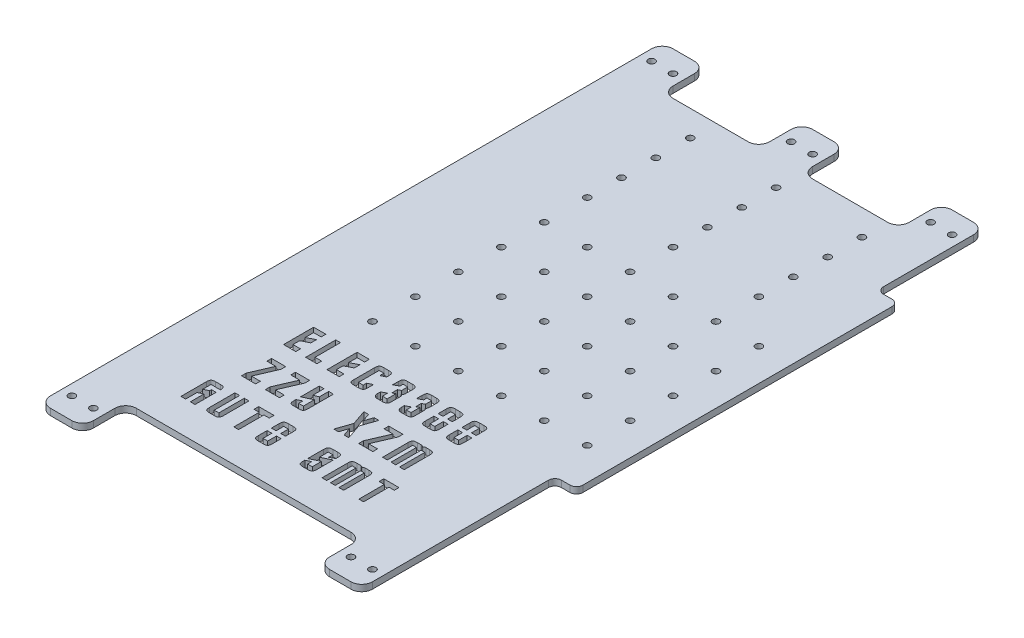
SolidWorks part; units mm, degrees
ref_plane "前视基准面" through (0, 0, 0) normal (0, 0, 1) x (1, 0, 0)
ref_plane "上视基准面" through (0, 0, 0) normal (0, 1, 0) x (1, 0, 0)
ref_plane "右视基准面" through (0, 0, 0) normal (1, 0, 0) x (0, 0, -1)
sketch "草图1" plane through (0, 0, 0) normal (0, 1, 0) x (1, 0, 0)
  line L19 (-35, 255) -> (75, 255) construction
  line L20 (-35, 255) -> (-35, 105) construction
  line L21 (-35, 105) -> (75, 105) construction
  line L22 (75, 255) -> (75, 105) construction
  line L23 (-140, 290) -> (140, 290) construction
  line L24 (-140, 290) -> (-140, 0) construction
  line L25 (-140, 0) -> (140, 0) construction
  line L26 (140, 290) -> (140, 0) construction
  line L27 (140, 290) -> (75, 290) construction
  line L28 (140, 290) -> (140, 240) construction
  line L29 (140, 240) -> (75, 240) construction
  line L30 (75, 290) -> (75, 240) construction
  line L31 (-140, 290) -> (-75, 290) construction
  line L32 (-140, 290) -> (-140, 240) construction
  line L33 (-140, 240) -> (-75, 240) construction
  line L34 (-75, 290) -> (-75, 240) construction
  line L35 (-75, 290) -> (-75, 0)
  line L37 (75, 0) -> (75, 90)
  line L38 (75, 90) -> (85, 90)
  line L39 (85, 90) -> (85, 240)
  line L40 (85, 240) -> (75, 240)
  line L41 (75, 240) -> (75, 290)
  line L42 (-30, 210) -> (10, 210) construction
  line L43 (-45, 261.5) -> (65, 261.5) construction
  line L44 (-45, 261.5) -> (-45, 206.5) construction
  line L45 (-45, 206.5) -> (65, 206.5) construction
  line L46 (65, 261.5) -> (65, 206.5) construction
  line L47 (-30, 210) -> (-30, 226) construction
  line L48 (-30, 110) -> (-10, 110) construction
  line L49 (-30, 110) -> (-30, 130) construction
  line L50 (-75, 290) -> (-55, 290)
  line L51 (-55, 290) -> (-55, 270)
  line L52 (-55, 270) -> (-10, 270)
  line L53 (-10, 270) -> (-10, 290)
  line L54 (-10, 290) -> (10, 290)
  line L55 (10, 290) -> (10, 270)
  line L56 (10, 270) -> (55, 270)
  line L57 (55, 270) -> (55, 290)
  line L58 (55, 290) -> (75, 290)
  line L59 (-75, 0) -> (-55, 0)
  line L60 (-55, 0) -> (-55, 20)
  line L61 (-55, 20) -> (-10, 20)
  line L62 (-10, 20) -> (-10, 0)
  line L63 (-10, 0) -> (10, 0)
  line L64 (10, 0) -> (10, 20)
  line L65 (10, 20) -> (55, 20)
  line L66 (55, 20) -> (55, 0)
  line L67 (55, 0) -> (75, 0)
  circle A0 centre (-30, 210) radius 1.6
  circle A1 centre (10, 210) radius 1.6
  circle A2 centre (50, 210) radius 1.6
  circle A3 centre (10, 226) radius 1.6
  circle A4 centre (50, 226) radius 1.6
  circle A5 centre (10, 242) radius 1.6
  circle A6 centre (50, 242) radius 1.6
  circle A7 centre (10, 258) radius 1.6
  circle A8 centre (50, 258) radius 1.6
  circle A9 centre (-30, 226) radius 1.6
  circle A10 centre (-30, 242) radius 1.6
  circle A11 centre (-30, 258) radius 1.6
  circle A12 centre (-30, 110) radius 1.6
  circle A13 centre (-10, 110) radius 1.6
  circle A14 centre (10, 110) radius 1.6
  circle A15 centre (30, 110) radius 1.6
  circle A16 centre (50, 110) radius 1.6
  circle A17 centre (70, 110) radius 1.6
  circle A18 centre (-10, 130) radius 1.6
  circle A19 centre (10, 130) radius 1.6
  circle A20 centre (30, 130) radius 1.6
  circle A21 centre (50, 130) radius 1.6
  circle A22 centre (70, 130) radius 1.6
  circle A23 centre (-10, 150) radius 1.6
  circle A24 centre (10, 150) radius 1.6
  circle A25 centre (30, 150) radius 1.6
  circle A26 centre (50, 150) radius 1.6
  circle A27 centre (70, 150) radius 1.6
  circle A28 centre (-10, 170) radius 1.6
  circle A29 centre (10, 170) radius 1.6
  circle A30 centre (30, 170) radius 1.6
  circle A31 centre (50, 170) radius 1.6
  circle A32 centre (70, 170) radius 1.6
  circle A33 centre (-10, 190) radius 1.6
  circle A34 centre (10, 190) radius 1.6
  circle A35 centre (30, 190) radius 1.6
  circle A36 centre (50, 190) radius 1.6
  circle A37 centre (70, 190) radius 1.6
  circle A38 centre (-30, 130) radius 1.6
  circle A39 centre (-30, 150) radius 1.6
  circle A40 centre (-30, 170) radius 1.6
  circle A41 centre (-30, 190) radius 1.6
  point P3 (0, 290)
  point P31 (10, 206.5)
  point P127 (0, 290)
  dimension "D22" = 3.2
  dimension "D29" = 3.2
  dimension "D1" = 105
  dimension "D2" = 35
  dimension "D3" = 290
  dimension "D4" = 105
  dimension "D5" = 75
  dimension "D6" = 280
  dimension "D7" = 140
  dimension "D8" = 65
  dimension "D9" = 50
  dimension "D10" = 50
  dimension "D11" = 75
  dimension "D12" = 150
  dimension "D13" = 10
  dimension "D14" = 20
  dimension "D15" = 55
  dimension "D16" = 110
  dimension "D19" = 90
  dimension "D20" = 40
  dimension "D21" = 16
  dimension "D23" = 3.5
  dimension "D24" = 6
  dimension "D26" = 90
  dimension "D27" = 20
  dimension "D28" = 20
  dimension "D30" = 5
  dimension "D31" = 5
  dimension "D32" = 20
  dimension "D33" = 5
  dimension "D34" = 20
  dimension "D35" = 20
  dimension "D36" = 20
  dimension "D37" = 20
  dimension "D38" = 20
  dimension "D39" = 20
  dimension "D40" = 20
  dimension "D41" = 90
  dimension "D17" = 3
  dimension "D18" = 4
  dimension "D25" = 5
extrude "凸台-拉伸1" add sketch "草图1" along normal blind 3 contours L66 L67 L37 L38 L39 L40 L41 L58 L57 L56 L55 L54 L53 L52 L51 L50 L35 L59 L60 L61 L62 L63 L64 L65 A41 A40 A39 A38 A37 A36 A35 A34 A33 A32 A31 A30 A29 region at (2.7814, 0, -145.492)
sketch "草图2" plane through (0, 3, 0) normal (0, 1, 0) x (1, 0, 0)
  line L0 (-75, 80) -> (75, 80) construction
  line L1 (75, 0) -> (75, 90) construction
  line L2 (-75, 290) -> (-75, 0) construction
  line L3 (10, 20) -> (55, 20) construction
  text T0 "ELEC3300\r\nZZY XZM\r\nAUTO SMT" font "Roddenberry" height 14
  point P3 (0, 0)
  point P4 (61.7213, 73.1926)
  point P5 (-56.3746, 80.1556)
  point P6 (75, 70.8846)
  point P9 (-75, 71.4828)
  dimension "D1" = 60
extrude "切除-拉伸3" cut sketch "草图2" against normal through all
sketch "草图4" plane through (0, 3, 0) normal (0, 1, 0) x (1, 0, 0)
  line L0 (-40.0089, 47.003) -> (-42.197, 47.003) construction
  line L1 (-40.0089, 47.003) -> (-37.0575, 47.003)
  line L2 (-40.0089, 47.003) -> (-40.0089, 45.003)
  line L3 (-40.0089, 45.003) -> (-37.0575, 45.003)
  line L4 (-37.0575, 47.003) -> (-37.0575, 45.003)
  line L6 (-11.8635, 43.4704) -> (-1.9233, 43.4704)
  line L7 (-11.8635, 43.4704) -> (-11.8635, 41.4704)
  line L8 (-11.8635, 41.4704) -> (-1.9233, 41.4704)
  line L9 (-1.9233, 43.4704) -> (-1.9233, 41.4704)
  line L10 (21.6611, 88.1453) -> (42.1209, 88.1453)
  line L11 (21.6611, 88.1453) -> (21.6611, 86.1453)
  line L12 (21.6611, 86.1453) -> (42.1209, 86.1453)
  line L13 (42.1209, 88.1453) -> (42.1209, 86.1453)
  dimension "D1" = 2
  dimension "D2" = 2
  dimension "D3" = 2
extrude "凸台-拉伸2" add sketch "草图4" against normal blind 3
sketch "草图5" plane through (0, 3, 0) normal (0, 1, 0) x (1, 0, 0)
  line L0 (-75, 290) -> (-75, 0) construction
  line L1 (-10, 20) -> (-10, 0) construction
  line L2 (55, 20) -> (55, 0) construction
  line L3 (-75, 0) -> (-55, 0) construction
  line L4 (-70, 10) -> (-70, 280) construction
  circle A0 centre (-70, 10) radius 1.6
  circle A1 centre (-5, 10) radius 1.6
  circle A2 centre (5, 10) radius 1.6
  circle A3 centre (60, 10) radius 1.6
  circle A4 centre (70, 10) radius 1.6
  circle A5 centre (-60, 10) radius 1.6
  circle A6 centre (-70, 280) radius 1.6
  circle A7 centre (-5, 280) radius 1.6
  circle A8 centre (5, 280) radius 1.6
  circle A9 centre (60, 280) radius 1.6
  circle A10 centre (70, 280) radius 1.6
  circle A11 centre (-60, 280) radius 1.6
  dimension "D1" = 3.2
  dimension "D2" = 10
  dimension "D3" = 5
  dimension "D4" = 10
  dimension "D5" = 5
  dimension "D6" = 10
  dimension "D7" = 5
  dimension "D8" = 10
  dimension "D10" = 270
  dimension "D9" = 2
extrude "切除-拉伸5" cut sketch "草图5" against normal through all
fillet "圆角1" radius 5 20 edges at (-75, 1.5, -290) (-55, 1.5, -290) (-55, 1.5, -270) (-10, 1.5, -290) (-10, 1.5, -270) (55, 1.5, -290) (55, 1.5, -270) (10, 1.5, -290) (10, 1.5, -270) (75, 1.5, -290) (75, 1.5, 0) (55, 1.5, 0) (55, 1.5, -20) (10, 1.5, -20) (10, 1.5, 0) (-10, 1.5, 0) (-10, 1.5, -20) (-55, 1.5, -20) (-55, 1.5, 0) (-75, 1.5, 0)
fillet "圆角2" radius 3 4 edges at (75, 1.5, -240) (85, 1.5, -240) (85, 1.5, -90) (75, 1.5, -90)
sketch "草图6" plane through (0, 3, 0) normal (0, 1, 0) x (1, 0, 0)
  line L1 (-15, 20) -> (18.0907, 20)
  line L2 (-15, 20) -> (-15, -1.1876)
  line L3 (-15, -1.1876) -> (18.0907, -1.1876)
  line L4 (18.0907, 20) -> (18.0907, -1.1876)
extrude "切除-拉伸6" cut sketch "草图6" against normal through all
